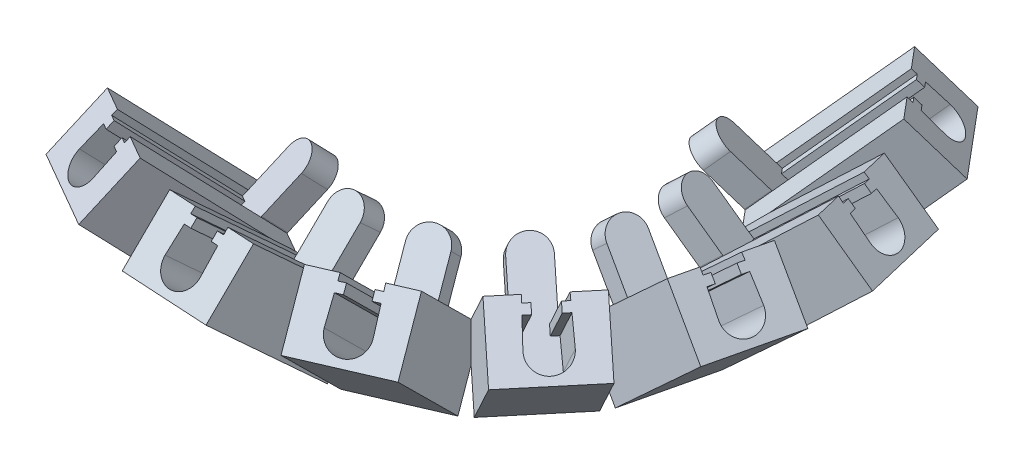
SolidWorks part; units mm, degrees
ref_plane "Front Plane" through (0, 0, 0) normal (0, 0, 1) x (1, 0, 0)
ref_plane "Top Plane" through (0, 0, 0) normal (0, 1, 0) x (1, 0, 0)
ref_plane "Right Plane" through (0, 0, 0) normal (1, 0, 0) x (0, 0, -1)
sketch "SkullCoords" plane through (0, 0, 0) normal (0, 1, 0) x (1, 0, 0)
  line L0 (0, 0) -> (1, 0)
  line L1 (1, 0) -> (1, 1)
  line L2 (1.2187, 1.1839) -> (0.7813, 0.8161)
  point P6 (0, 0)
  dimension "D1" = 1
  dimension "D2" = 1
ref_plane "Plane1" through (-0.0784, 0, -0.0932) normal (-0.6436, 0, -0.7654) x (-0.7654, 0, 0.6436)
sketch "TubingProfile" plane through (-0.0784, 0, -0.0932) normal (-0.6436, 0, -0.7654) x (-0.7654, 0, 0.6436)
  line L0 (-1.409, 0) -> (-1.409, 4)
  line L1 (-3.1142, 7.8653) -> (-16.409, 20)
  line L2 (-18.0943, 18.1535) -> (-14.7236, 21.8465)
  line L3 (-1.409, 0) -> (-1.409, 11.4855) construction
  line L4 (-1.409, 0) -> (-27.1149, 0) construction
  arc A0 (-3.1142, 7.8653) -> (-1.409, 4) centre (-6.6423, 4) cw
  point P10 (-9.7616, 13.9327)
  point P11 (0, 0)
  dimension "D2" = 18
  dimension "D3" = 15
  dimension "D4" = 5
  dimension "D5" = 20
  dimension "D6" = 42.388
  dimension "D7" = 42.388
ref_plane "PerpendicularToTravel" through (7.3928, 13.9327, -6.3758) normal (0.5653, 0.6741, -0.4754) x (0.8233, -0.4966, 0.2748)
sketch "ShuttleGuide" plane through (7.3928, 13.9327, -6.3758) normal (0.5653, 0.6741, -0.4754) x (0.8233, -0.4966, 0.2748)
  line L0 (0, 0) -> (2.9586, 3.2568) construction
  line L1 (1.681, 1.8505) -> (-1.681, -1.8505) construction
  line L2 (0.7402, -0.6724) -> (-0.7402, 0.6724) construction
  line L3 (-0.7402, 0.6724) -> (-1.0764, 0.3023)
  line L4 (0.7402, -0.6724) -> (0.404, -1.0425)
  line L5 (3.7543, 2.534) -> (2.1629, 3.9796) construction
  line L6 (2.085, 0.808) -> (0.6046, 2.1528) construction
  line L7 (-0.7402, 0.6724) -> (0.6046, 2.1528)
  line L8 (0.7402, -0.6724) -> (2.085, 0.808)
  line L9 (2.085, 0.808) -> (3.7543, 2.534) construction
  line L10 (2.1629, 3.9796) -> (0.6046, 2.1528) construction
  line L11 (2.711, 1.4552) -> (2.4149, 1.7242)
  line L12 (2.4149, 1.7242) -> (2.0787, 1.3541)
  line L13 (2.0787, 1.3541) -> (2.3632, 1.0956)
  line L14 (1.189, 2.8379) -> (1.485, 2.5689)
  line L15 (1.485, 2.5689) -> (1.1488, 2.1988)
  line L16 (1.1488, 2.1988) -> (0.8643, 2.4573)
  line L17 (3.7543, 2.534) -> (2.711, 1.4552)
  line L18 (2.3632, 1.0956) -> (2.085, 0.808)
  line L19 (2.1629, 3.9796) -> (1.189, 2.8379)
  line L20 (0.8643, 2.4573) -> (0.6046, 2.1528)
  line L21 (2.1133, 0.8372) -> (3.2781, -0.221)
  line L22 (3.2781, -0.221) -> (5.8732, 2.6357)
  line L23 (5.8732, 2.6357) -> (2.0612, 6.0985)
  line L24 (2.0612, 6.0985) -> (-0.5338, 3.2419)
  line L25 (-0.5338, 3.2419) -> (0.631, 2.1837)
  circle A0 centre (0, 0) radius 0.2511
  arc A2 (0.404, -1.0425) -> (-1.0764, 0.3023) centre (-0.3362, -0.3701) cw
  arc A3 (3.7543, 2.534) -> (2.1629, 3.9796) centre (2.9586, 3.2568) ccw
  point P15 (1.3448, 1.4804)
  dimension "D1" = 4.4
  dimension "D3" = 0.5
  dimension "D4" = 2.15
  dimension "D5" = 2.4
  dimension "D6" = 0.5
  dimension "D7" = 1.5
  dimension "D8" = 0.4
  dimension "D9" = 1.5
  dimension "D10" = 1.5
extrude "Boss-Extrude1" add sketch "ShuttleGuide" along normal blind 9 contours A3 L17 L11 L12 L13 L18 L21 L22 L23 L24 L25 L20 L16 L15 L14 L19 region at (7.3413, 12.359, -8.6688)
extrude "Boss-Extrude2" add sketch "ShuttleGuide<3>" along normal blind 1.5 contours A2 L3 L7 L20 L16 L15 L14 L19 A3 L17 L11 L12 L13 L18 L8 L4
sketch "ShuttleGuide<3>" plane through (7.3928, 13.9327, -6.3758) normal (0.5653, 0.6741, -0.4754) x (0.8233, -0.4966, 0.2748) same geometry as "ShuttleGuide"
pattern_circular "CirPattern2" count 7 over 160 about axis through (1, 0, -1) along (0, 1, 0) of "Boss-Extrude2", "Boss-Extrude1" reverse direction yes
equation "\"30gBendRadius\"=4"
equation "\"Travel\"= 9"
equation "\"D2@TubingProfile\"=\"DoubleTravel\""
equation "\"NutLengthHoleToHole\"=4.4"
equation "\"D1@ShuttleGuide\" = \"NutLengthHoleToHole\""
equation "\"NutWidth\"=2"
equation "\"D2@ShuttleGuide\" = \"NutWidth\""
equation "\"D1@Boss-Extrude1\"=\"Travel\""
equation "\"DoubleTravel\"= \"Travel\" * 2"
